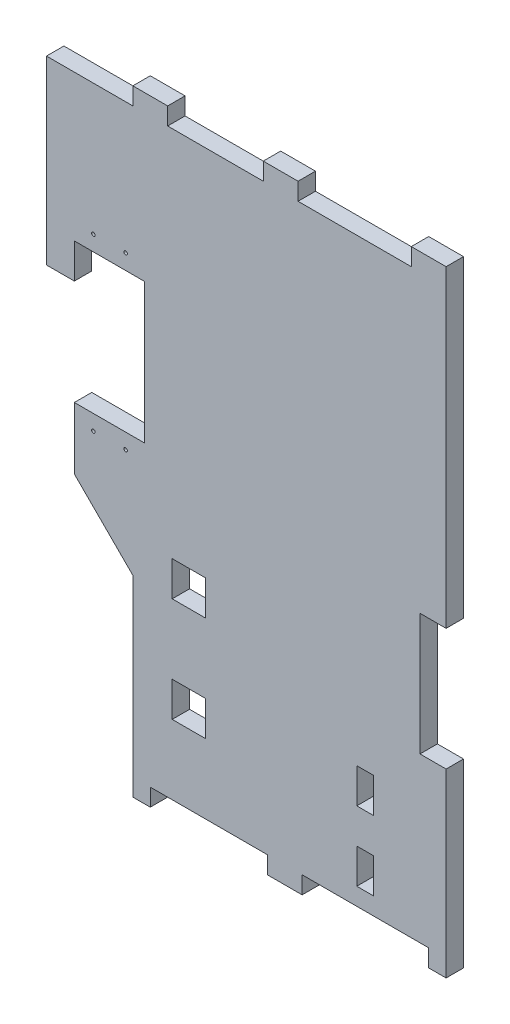
SolidWorks part; units mm, degrees
material "Balsa"
ref_plane "Plan de face" through (0, 0, 0) normal (0, 0, 1) x (1, 0, 0)
ref_plane "Plan de dessus" through (0, 0, 0) normal (0, 1, 0) x (1, 0, 0)
ref_plane "Plan de droite" through (0, 0, 0) normal (1, 0, 0) x (0, 0, -1)
sketch "Esquisse1" plane through (0, 0, 0) normal (0, 0, 1) x (1, 0, 0)
  line L0 (90, 82) -> (90, 167)
  line L1 (5, 0) -> (90, 0)
  line L2 (0, 0) -> (0, 167)
  line L3 (10, 167) -> (80, 167)
  line L4 (90, 0) -> (90, 47)
  line L5 (90, 82) -> (82.5, 82)
  line L6 (0, 167) -> (0, 172)
  line L7 (0, 172) -> (10, 172)
  line L8 (10, 167) -> (10, 172)
  line L9 (0, 0) -> (0, -5)
  line L10 (90, 167) -> (90, 172)
  line L11 (90, 172) -> (80, 172)
  line L12 (80, 167) -> (80, 172)
  line L13 (0, -5) -> (5, -5)
  line L14 (5, 0) -> (5, -5)
  line L15 (64.3348, 35) -> (64.3348, 25)
  line L16 (90, 47) -> (82.5, 47)
  line L17 (82.5, 82) -> (82.5, 47)
  line L18 (64.3348, 35) -> (69.1423, 35)
  line L19 (64.3348, 25) -> (69.1423, 25)
  line L20 (69.1423, 35) -> (69.1423, 25)
  line L21 (71.3405, 35) -> (66.533, 35) construction
  line L22 (64.3348, 35) -> (64.3348, 25) construction
  line L23 (69.1423, 35) -> (69.1423, 25) construction
  line L24 (18.5374, 30) -> (3.1837, 30) construction
  line L25 (64.3348, 15) -> (69.1423, 15)
  line L26 (64.3348, 15) -> (64.3348, 5)
  line L27 (64.3348, 5) -> (69.1423, 5)
  line L28 (69.1423, 15) -> (69.1423, 5)
  line L29 (11.3034, 30) -> (20.8832, 30)
  line L30 (11.3034, 30) -> (11.3034, 20)
  line L31 (11.3034, 20) -> (20.8832, 20)
  line L32 (20.8832, 30) -> (20.8832, 20)
  line L33 (3.1837, 20) -> (18.5374, 20) construction
  line L36 (21.1471, 30) -> (5.7933, 30) construction
  line L37 (11.3034, 60) -> (20.8832, 60)
  line L38 (11.3034, 60) -> (11.3034, 50)
  line L39 (11.3034, 50) -> (20.8832, 50)
  line L40 (20.8832, 60) -> (20.8832, 50)
  dimension "D1" = 167
  dimension "D2" = 90
  dimension "D3" = 10
  dimension "D4" = 5
  dimension "D5" = 5
  dimension "D6" = 7.5
  dimension "D7" = 35
  dimension "D8" = 82
  dimension "D9" = 10
  dimension "D10" = 10
  dimension "D11" = 10
extrude "Boss.-Extru.1" add sketch "Esquisse1" along normal blind 5
sketch "Esquisse2" plane through (0, 0, 5) normal (0, 0, 1) x (1, 0, 0)
  line L0 (0, 172) -> (0, -5) construction
  line L1 (0, 167) -> (-16.8145, 167)
  line L2 (0, 167) -> (0, 50.1855)
  line L3 (0, 50.1855) -> (-16.8145, 67)
  line L4 (-16.8145, 167) -> (-16.8145, 67)
  line L6 (80, 167) -> (10, 167) construction
  dimension "D1" = 16.8145
  dimension "D2" = 135
  dimension "D3" = 100
extrude "Boss.-Extru.2" add sketch "Esquisse2" against normal blind 5
sketch "Esquisse3" plane through (0, 0, 5) normal (0, 0, 1) x (1, 0, 0)
  line L0 (0, 167) -> (-16.8145, 167) construction
  line L1 (3.3855, 125) -> (-16.8145, 125)
  line L2 (3.3855, 125) -> (3.3855, 84.8)
  line L3 (3.3855, 84.8) -> (-16.8145, 84.8)
  line L4 (-16.8145, 125) -> (-16.8145, 84.8)
  line L5 (-16.8145, 167) -> (-16.8145, 67) construction
  dimension "D1" = 42
  dimension "D2" = 20.2
  dimension "D3" = 40.2
extrude "Enlèv. mat.-Extru.1" cut sketch "Esquisse3" against normal blind 5
sketch "Esquisse4" plane through (0, 0, 5) normal (0, 0, 1) x (1, 0, 0)
  line L0 (5, 0) -> (90, 0) construction
  line L1 (-16.8145, 167) -> (-24.8145, 167)
  line L2 (-16.8145, 167) -> (-16.8145, 115)
  line L3 (-16.8145, 115) -> (-24.8145, 115)
  line L4 (-24.8145, 167) -> (-24.8145, 115)
  line L5 (38.6337, 0) -> (48.6337, 0)
  line L6 (38.6337, 0) -> (38.6337, -5)
  line L7 (38.6337, -5) -> (48.6337, -5)
  line L8 (48.6337, 0) -> (48.6337, -5)
  line L9 (92.5017, -5) -> (-34.7153, -5) construction
  line L10 (90, 0) -> (90, 47) construction
  line L11 (90, 0) -> (85, 0)
  line L12 (90, 0) -> (90, -5)
  line L13 (90, -5) -> (85, -5)
  line L14 (85, 0) -> (85, -5)
  line L15 (80, 167) -> (10, 167) construction
  line L16 (0, 50.1855) -> (0, -5) construction
  line L17 (37.4664, 167) -> (47.4664, 167)
  line L18 (37.4664, 167) -> (37.4664, 172)
  line L19 (37.4664, 172) -> (47.4664, 172)
  line L20 (47.4664, 167) -> (47.4664, 172)
  dimension "D1" = 8
  dimension "D2" = 52
  dimension "D3" = 5
  dimension "D4" = 5
  dimension "D5" = 10
  dimension "D6" = 38.6337
  dimension "D7" = 5
  dimension "D8" = 10
extrude "Boss.-Extru.3" add sketch "Esquisse4" against normal blind 5
sketch "Esquisse5" plane through (0, 0, 5) normal (0, 0, 1) x (1, 0, 0)
  circle A0 centre (-11.3395, 129.4) radius 0.5
  circle A1 centre (-2.0895, 129.4) radius 0.5
  circle A2 centre (-11.3395, 80.4) radius 0.5
  circle A3 centre (-2.0895, 80.4) radius 0.5
  dimension "D1" = 1
extrude "Enlèv. mat.-Extru.2" cut sketch "Esquisse5" against normal blind 5
